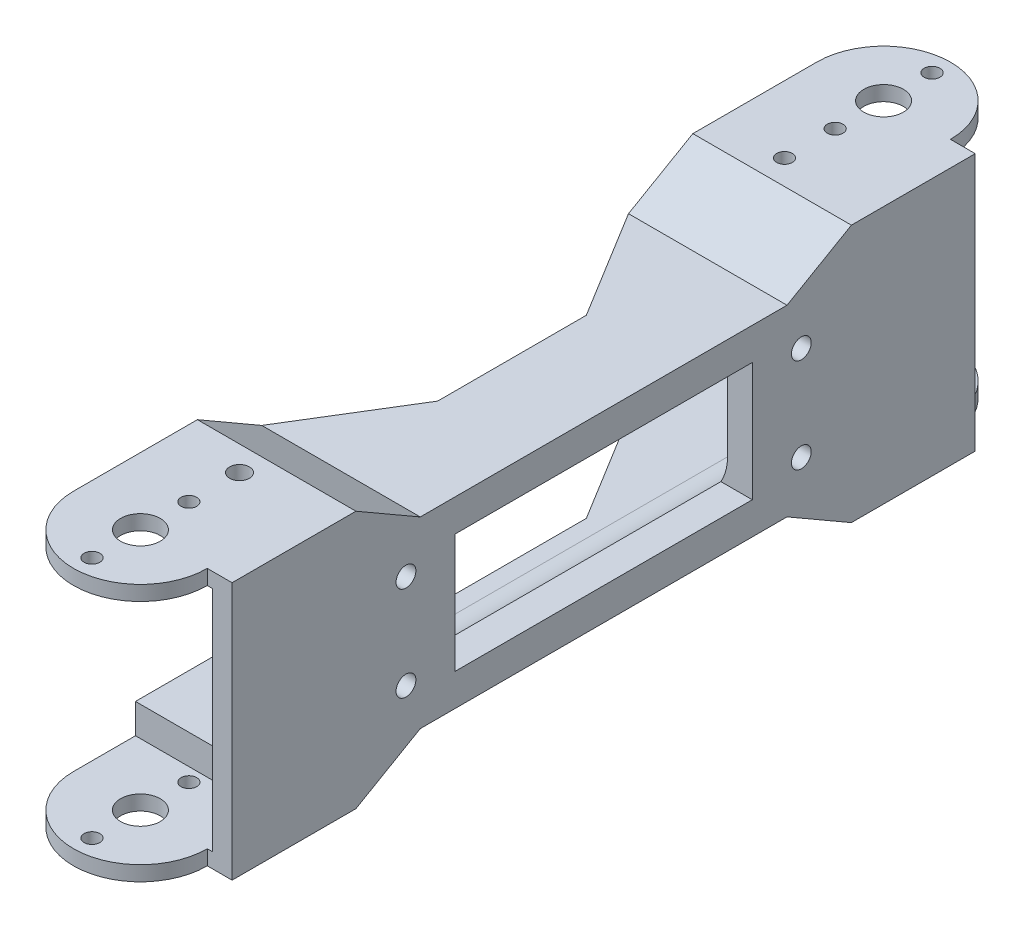
SolidWorks part; units mm, degrees
material "POM Acetal Copolymer"
ref_plane "Front Plane" through (0, 0, 0) normal (0, 0, 1) x (1, 0, 0)
ref_plane "Top Plane" through (0, 0, 0) normal (0, 1, 0) x (1, 0, 0)
ref_plane "Right Plane" through (0, 0, 0) normal (1, 0, 0) x (0, 0, -1)
sketch "Sketch1" plane through (0, 0, 0) normal (0, 1, 0) x (1, 0, 0)
  line L0 (0, 75) -> (0, -75) construction
  line L2 (-13.5, 75) -> (-13.5, -75)
  line L4 (13.5, 75) -> (13.5, -75)
  arc A0 (13.5, 75) -> (-13.5, 75) centre (0, 75) ccw
  arc A1 (-13.5, -75) -> (13.5, -75) centre (0, -75) ccw
  circle A2 centre (0, -55) radius 2
  point P5 (0, 0)
  dimension "D3" = 4
  dimension "D1" = 150
  dimension "D2" = 27
  dimension "D4" = 20
extrude "Boss-Extrude1" add sketch "Sketch1" along normal mid plane 52
sketch "Sketch3" plane through (-13.5, 0, 0) normal (-1, 0, 0) x (0, 0, 1)
  line L0 (-50, 26) -> (-37.0096, 18.5)
  line L1 (-75, 26) -> (75, 26) construction
  line L2 (-37.0096, 18.5) -> (37.0096, 18.5)
  line L3 (37.0096, 18.5) -> (50, 26)
  line L4 (50, 26) -> (-50, 26)
  line L5 (-75, 26) -> (-75, -26) construction
  point P6 (0, 18.5)
  point P7 (0, 26)
  dimension "D1" = 7.5
  dimension "D2" = 30
  dimension "D3" = 25
extrude "Cut-Extrude1" cut sketch "Sketch3" against normal through all both and the other way through all
mirror "Mirror1" about plane through (0, 0, 0) normal (0, 1, 0) of "Cut-Extrude1"
sketch "Sketch4" plane through (-13.5, 0, 0) normal (-1, 0, 0) x (0, 0, 1)
  line L0 (-88.5, 26) -> (-88.5, -26) construction
  line L1 (62.5, 23) -> (88.5, 23)
  line L2 (-88.5, 23) -> (-62.5, 23)
  line L3 (-88.5, 23) -> (-88.5, 17)
  line L4 (-88.5, 17) -> (-62.5, 17)
  line L5 (-62.5, 23) -> (-62.5, 17)
  line L6 (-88.5, -23) -> (-62.5, -23)
  line L7 (-88.5, -23) -> (-88.5, -17)
  line L8 (-88.5, -17) -> (-62.5, -17)
  line L9 (-62.5, -23) -> (-62.5, -17)
  line L10 (62.5, 23) -> (62.5, 17)
  line L11 (62.5, 17) -> (88.5, 17)
  line L12 (88.5, 23) -> (88.5, 17)
  line L13 (62.5, -17) -> (88.5, -17)
  line L14 (62.5, -17) -> (62.5, -23)
  line L15 (62.5, -23) -> (88.5, -23)
  line L16 (88.5, -17) -> (88.5, -23)
  line L18 (88.5, -26) -> (88.5, 26) construction
  line L19 (-62.5, 17) -> (-62.5, -17) construction
  line L20 (62.5, 17) -> (62.5, -17) construction
  point P20 (-62.5, 0)
  dimension "D1" = 26
  dimension "D2" = 6
  dimension "D3" = 34
extrude "Cut-Extrude2" cut sketch "Sketch4" against normal through all both
sketch "Sketch5" plane through (-13.5, 0, 0) normal (-1, 0, 0) x (0, 0, 1)
  line L1 (-88.5, 17) -> (88.5, 17)
  line L2 (-88.5, 17) -> (-88.5, -17)
  line L3 (-88.5, -17) -> (88.5, -17)
  line L4 (88.5, 17) -> (88.5, -17)
extrude "Cut-Extrude3" cut sketch "Sketch5" against normal offset from surface (22 mm away) 5 up to face at (13.5, 0, 0)
sketch "Sketch6" plane through (8.5, 0, 0) normal (-1, 0, 0) x (0, 0, 1)
  line L0 (62.5, -17) -> (-62.5, -17) construction
  line L1 (85.4881, 17) -> (62.5, 17)
  line L2 (85.4881, 17) -> (85.4881, -17)
  line L3 (85.4881, -17) -> (62.5, -17)
  line L4 (62.5, 17) -> (62.5, -17)
  line L5 (62.5, -17) -> (62.5, -23) construction
extrude "Cut-Extrude4" cut sketch "Sketch6" against normal through all
sketch "Sketch7" plane through (8.5, 0, 0) normal (-1, 0, 0) x (0, 0, 1)
  line L1 (-85.4881, 17) -> (-62.5, 17)
  line L2 (-85.4881, 17) -> (-85.4881, -17)
  line L3 (-85.4881, -17) -> (-62.5, -17)
  line L4 (-62.5, 17) -> (-62.5, -17)
extrude "Cut-Extrude5" cut sketch "Sketch7" against normal through all
hole_wizard "1/8 (0.125) Diameter Hole1" positions "Sketch11" profile "Sketch12" hole size "1/8" standard "ANSI Inch"
sketch "Sketch11" plane through (0, 26, 0) normal (0, 1, 0) x (1, 0, 0)
  line L0 (9.779, -75) -> (-9.779, -75) construction
  line L2 (0, -65.221) -> (0, -84.779) construction
  arc A0 (-13.5, -75) -> (13.5, -75) centre (0, -75) ccw construction
  point P0 (0, -65.221)
  point P6 (0, -84.779)
  point P17 (0, -75)
  point P18 (0, -75)
  dimension "D1" = 19.558
sketch "Sketch12" plane through (0, 26, 65.221) normal (1, 0, 0) x (0, 0, 1)
  line L0 (0, 0) -> (0, 3.9539)
  line L1 (0, 3.9539) -> (1.5875, 3)
  line L2 (1.5875, 3) -> (1.5875, 0)
  line L5 (1.5875, 0) -> (0, 0)
  line L10 (0, 3.9539) -> (-1.5875, 3) construction
  line L11 (0, -6.35) -> (0, 107.95) construction
  dimension "Hole Dia." = 3.175
  dimension "Hole Depth" = 3
  dimension "Drill Angle" = 118
mirror "Mirror5" about plane through (0, 0, 0) normal (0, 1, 0) of "1/8 (0.125) Diameter Hole1"
mirror "Mirror3" about plane through (0, 0, 0) normal (0, 0, 1) of "1/8 (0.125) Diameter Hole1"
sketch "Sketch13" plane through (0, -26, 0) normal (0, -1, 0) x (1, 0, 0)
  circle A0 centre (0, -75) radius 4
  arc A1 (-13.5, -75) -> (13.5, -75) centre (0, -75) ccw construction
  dimension "D1" = 8
extrude "Cut-Extrude6" cut sketch "Sketch13" against normal through all both and the other way through all
mirror "Mirror4" about plane through (0, 0, 0) normal (0, 0, 1) of "Cut-Extrude6"
sketch "Sketch14" plane through (13.5, 0, 0) normal (1, 0, 0) x (0, 0, -1)
  line L0 (-75, 26) -> (-75, 23)
  line L1 (-75, 23) -> (-62.5, 23)
  line L2 (-62.5, 23) -> (-62.5, -23)
  line L3 (-62.5, -23) -> (-75, -23)
  line L4 (-75, -23) -> (-75, -26)
  line L5 (-75, -26) -> (-50, -26)
  line L6 (-50, -26) -> (-37.0096, -18.5)
  line L7 (-37.0096, -18.5) -> (37.0096, -18.5)
  line L8 (37.0096, -18.5) -> (50, -26)
  line L12 (62.5, -23) -> (62.5, 23)
  line L13 (62.5, 23) -> (75, 23)
  line L14 (75, 23) -> (75, 26)
  line L15 (75, 26) -> (50, 26)
  line L16 (50, 26) -> (37.0096, 18.5)
  line L17 (37.0096, 18.5) -> (-37.0096, 18.5)
  line L18 (-37.0096, 18.5) -> (-50, 26)
  line L19 (-50, 26) -> (-75, 26)
  line L20 (62.5, -23) -> (75, -23)
  line L21 (75, -23) -> (75, -26)
  line L22 (75, -26) -> (50, -26)
extrude "Boss-Extrude2" add sketch "Sketch14" along normal blind 5
sketch "Sketch15" plane through (8.5, 0, 0) normal (-1, 0, 0) x (0, 0, 1)
  line L1 (-62.5, 17) -> (62.5, 17)
  line L2 (-62.5, 17) -> (-62.5, -17)
  line L3 (-62.5, -17) -> (62.5, -17)
  line L4 (62.5, 17) -> (62.5, -17)
extrude "Cut-Extrude7" cut sketch "Sketch15" against normal blind 5
sketch "Sketch17" plane through (0, 0, 62.5) normal (0, 0, 1) x (1, 0, 0)
  line L0 (18.5, -26) -> (13.5, -26) construction
  line L1 (18.5, 26) -> (14.5, 26)
  line L2 (18.5, 26) -> (18.5, -26)
  line L3 (18.5, -26) -> (14.5, -26)
  line L4 (14.5, 26) -> (14.5, -26)
  dimension "D1" = 4
extrude "Boss-Extrude4" add sketch "Sketch17" along normal up to surface (12.5 mm away) up to face at (16, 24.5, 75)
mirror "Mirror6" about plane through (0, 0, 0) normal (0, 1, 0) of "Mirror3"
sketch "Sketch19" plane through (18.5, 0, 0) normal (1, 0, 0) x (0, 0, -1)
  line L0 (-39.899, 9.525) -> (-39.899, -9.525) construction
  line L3 (-75, 26) -> (-75, -26) construction
  circle A0 centre (-39.899, 9.525) radius 2
  circle A1 centre (-39.899, -9.525) radius 2
  point P4 (-39.899, 0)
  dimension "D2" = 4
  dimension "D1" = 19.05
  dimension "D3" = 35.101
extrude "Cut-Extrude11" cut sketch "Sketch19" against normal blind 10
sketch "Sketch18" plane through (0, 26, 0) normal (0, 1, 0) x (1, 0, 0)
  circle A0 centre (0, 55) radius 1.5875
  circle A2 centre (0, 75) radius 4 construction
  dimension "D1" = 3.175
  dimension "D2" = 20
extrude "Cut-Extrude8" cut sketch "Sketch18" against normal up to surface (52 mm away) up to face at (0, -26, -66.8085)
sketch "Sketch20" plane through (13.5, 0, 0) normal (-1, 0, 0) x (0, 0, 1)
  line L1 (-30, 12) -> (30, 12)
  line L2 (-30, 12) -> (-30, -12)
  line L3 (-30, -12) -> (30, -12)
  line L4 (30, 12) -> (30, -12)
  point P4 (30, 0)
  point P8 (0, -12)
  dimension "D1" = 60
  dimension "D2" = 24
extrude "Cut-Extrude10" cut sketch "Sketch20" against normal blind 10
mirror "Mirror7" about plane through (0, 0, 0) normal (0, 0, 1) of "Cut-Extrude11"
sketch "Sketch21" plane through (0, 18.5, 0) normal (0, 1, 0) x (1, 0, 0)
  line L0 (-13.5, 37.0096) -> (0, 15)
  line L2 (0, 15) -> (0, -15)
  line L3 (0, -15) -> (-13.5, -37.0096)
  line L4 (-13.5, -37.0096) -> (-13.5, 37.0096)
  line L5 (18.5, 37.0096) -> (-13.5, 37.0096) construction
  point P4 (-13.5, 0)
  point P9 (0, 0)
  dimension "D1" = 30
extrude "Cut-Extrude12" cut sketch "Sketch21" against normal up to surface (37 mm away)
sketch "Sketch22" plane through (0, 0, -62.5) normal (0, 0, -1) x (-1, 0, 0)
  line L1 (-18.5, 23) -> (-13.5, 23)
  line L2 (-18.5, 23) -> (-18.5, -23)
  line L3 (-18.5, -23) -> (-13.5, -23)
  line L4 (-13.5, 23) -> (-13.5, -23)
extrude "Boss-Extrude5" add sketch "Sketch22" along normal up to surface (12.5 mm away) up to face at (16, 24.5, -75)
fillet "Fillet1" radius 10 2 edges at (13.5, 17, 0) (13.5, -17, 0)
